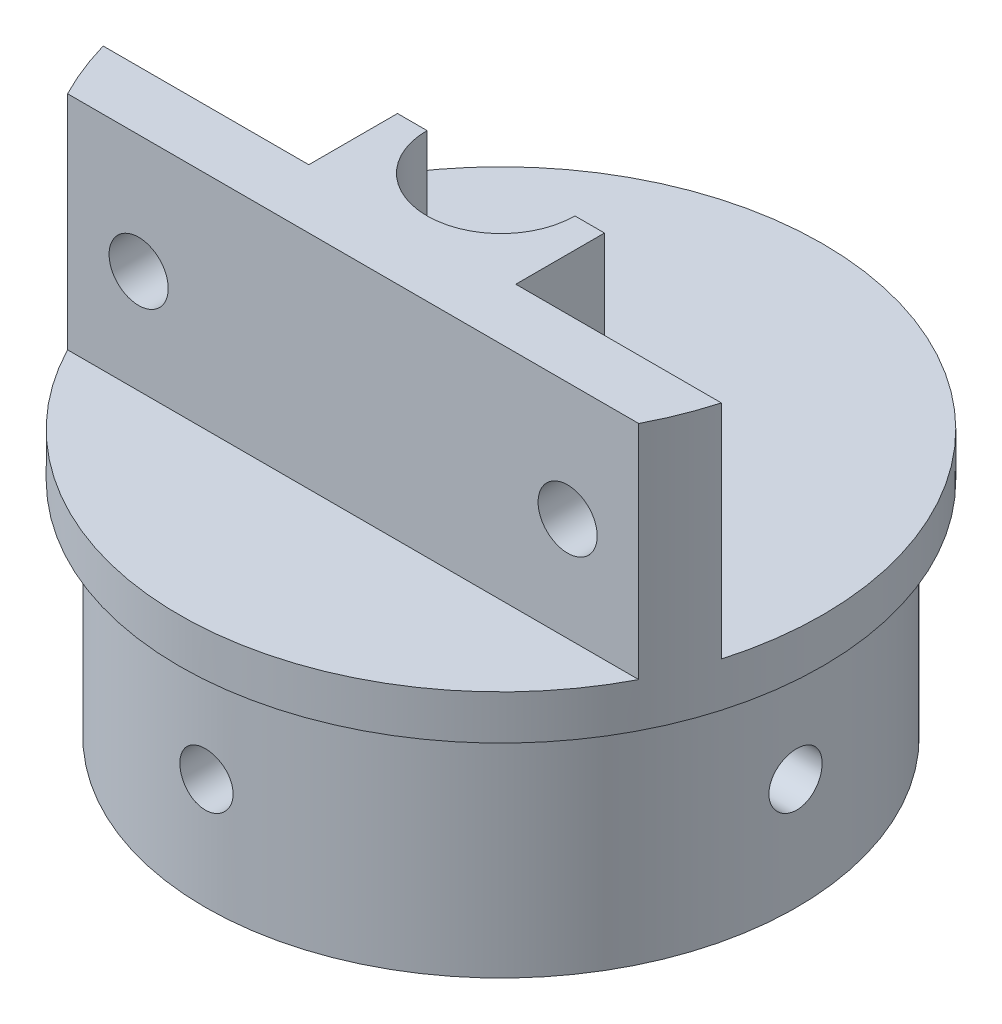
SolidWorks part; units mm, degrees
ref_plane "Front Plane" through (0, 0, 0) normal (0, 0, 1) x (1, 0, 0)
ref_plane "Top Plane" through (0, 0, 0) normal (0, 1, 0) x (1, 0, 0)
ref_plane "Right Plane" through (0, 0, 0) normal (1, 0, 0) x (0, 0, -1)
sketch "Sketch1" plane through (0, 0, 0) normal (0, 1, 0) x (1, 0, 0)
  line L0 (0, 0) -> (25.4, 0) construction
  line L1 (21.9604, 6.35) -> (14.3404, 3.175)
  line L2 (14.3404, 3.175) -> (14.3404, -3.175)
  line L3 (14.3404, -3.175) -> (21.9604, -6.35)
  line L5 (21.9604, 6.35) -> (21.9604, -6.35) construction
  line L6 (6.35, -21.9604) -> (3.175, -14.3404)
  line L7 (3.175, -14.3404) -> (-3.175, -14.3404)
  line L8 (-3.175, -14.3404) -> (-6.35, -21.9604)
  line L9 (-21.9604, -6.35) -> (-14.3404, -3.175)
  line L10 (-14.3404, -3.175) -> (-14.3404, 3.175)
  line L11 (-14.3404, 3.175) -> (-21.9604, 6.35)
  line L12 (-6.35, 21.9604) -> (-3.175, 14.3404)
  line L13 (-3.175, 14.3404) -> (3.175, 14.3404)
  line L14 (3.175, 14.3404) -> (6.35, 21.9604)
  circle A0 centre (0, 0) radius 27.6225 construction
  circle A1 centre (0, 0) radius 25.4
  circle A2 centre (0, 0) radius 22.86
  point P9 (14.3404, 0)
  point P11 (21.9604, 0)
  point P27 (0, 0)
  dimension "D1" = 55.245
  dimension "D2" = 2.2225
  dimension "D3" = 2.54
  dimension "D4" = 6.35
  dimension "D5" = 12.7
  dimension "D6" = 7.62
  dimension "D7" = 4
extrude "tube_connection_ring" add sketch "Sketch1" along normal blind 19.05 contours L14 A2 L12 L13 | L11 A2 L9 L10 | L8 A2 L6 L7 | L3 A2 L1 L2 | A1 A2
ref_plane "Plane1" through (25.4, 0, 0) normal (1, 0, 0) x (0, 0, -1)
sketch "Sketch6" plane through (25.4, 0, 0) normal (1, 0, 0) x (0, 0, -1)
  line L0 (0, 0) -> (0, 9.525) construction
  circle A0 centre (0, 9.525) radius 2.286
  point P4 (0, 9.525)
  dimension "D2" = 4.572
  dimension "D1" = 9.525
extrude "screw_hole" cut sketch "Sketch6" against normal blind 19.05
sketch "Sketch11" plane through (25.4, 0, 0) normal (1, 0, 0) x (0, 0, -1)
  line L0 (0, 9.525) -> (0, 14.9509) construction
  line L1 (0, 4.0991) -> (4.699, 6.812)
  line L2 (4.699, 6.812) -> (4.699, 12.238)
  line L3 (4.699, 12.238) -> (0, 14.9509)
  line L4 (0, 14.9509) -> (-4.699, 12.238)
  line L5 (-4.699, 12.238) -> (-4.699, 6.812)
  line L6 (-4.699, 6.812) -> (0, 4.0991)
  circle A0 centre (0, 9.525) radius 4.699 construction
  dimension "D1" = 9.398
extrude "nut_press_fit_hole" cut sketch "Sketch11" along normal blind 3.81 from surface at -11.0596 starting at face at (14.3404, 9.525, -2.286)
pattern_circular "CirPattern1" count 4 over 360 about axis through (0, 0, 0) along (0, 1, 0) of "screw_hole", "nut_press_fit_hole"
chamfer "screw_hole_chamfer" distance 2.54 angle 45 8 edges at (21.9604, 9.525, 6.35) (6.35, 9.525, 21.9604) (-6.35, 9.525, 21.9604) (21.9604, 9.525, -6.35) (-21.9604, 9.525, 6.35) (-21.9604, 9.525, -6.35) (-6.35, 9.525, -21.9604) (6.35, 9.525, -21.9604)
sketch "Sketch12" plane through (0, 19.05, 0) normal (0, 1, 0) x (1, 0, 0)
  circle A0 centre (0, 0) radius 27.6225
  circle A2 centre (0, 0) radius 3.302
  dimension "D1" = 55.245
  dimension "D2" = 6.604
extrude "top_plate" add sketch "Sketch12" along normal blind 3.81
sketch "Sketch13" plane through (0, 22.86, 0) normal (0, 1, 0) x (1, 0, 0)
  line L1 (26.5507, -7.62) -> (-26.5507, -7.62) construction
  line L2 (14.2621, -28.2316) -> (23.8379, -28.2316) construction
  line L3 (14.2621, -28.2316) -> (14.2621, -39.6616) construction
  line L4 (14.2621, -39.6616) -> (23.8379, -39.6616) construction
  line L5 (23.8379, -28.2316) -> (23.8379, -39.6616) construction
  line L6 (-27.6225, 0) -> (27.6225, 0) construction
  line L7 (27.6225, 6.35) -> (27.6225, -6.35) construction
  line L8 (19.05, 20.0025) -> (19.05, -20.0025) construction
  line L14 (0, -27.6225) -> (0, 0) construction
  line L15 (24.5298, -12.7) -> (-24.5298, -12.7)
  line L22 (26.5507, -7.62) -> (8.89, -7.62)
  line L23 (8.89, -7.62) -> (8.89, 0)
  line L24 (-8.89, 0) -> (-8.89, -7.62)
  line L25 (-8.89, -7.62) -> (-26.5507, -7.62)
  line L26 (-8.89, 0) -> (-6.35, 0)
  line L27 (6.35, 0) -> (8.89, 0)
  circle A0 centre (0, 0) radius 6.35
  circle A1 centre (0, 0) radius 27.6225 construction
  arc A3 (26.5507, -7.62) -> (24.5298, -12.7) centre (0, 0) cw
  arc A4 (-24.5298, -12.7) -> (-26.5507, -7.62) centre (0, 0) ccw
  arc A5 (-24.5298, -12.7) -> (-26.5507, -7.62) centre (0, 0) cw
  point P10 (27.6225, 0)
  point P16 (19.05, -28.2316)
  point P22 (6.35, 0)
  point P27 (-6.35, 0)
  dimension "D4" = 1.27
  dimension "D5" = 12.7
  dimension "D8" = 2.54
  dimension "D1" = 11.43
  dimension "D2" = 9.5758
  dimension "D3" = 12.7
  dimension "D6" = 19.05
  dimension "D7" = 5.08
  dimension "D9" = 2.54
extrude "hinge_hole" add sketch "Sketch13" along normal blind 19.05
sketch "Sketch14" plane through (0, 0, 12.7) normal (0, 0, 1) x (1, 0, 0)
  line L0 (18.4243, 22.86) -> (18.4243, 31.75) construction
  line L1 (27.6225, 22.86) -> (-27.6225, 22.86) construction
  line L2 (0, 22.86) -> (0, 41.91) construction
  line L3 (24.5298, 41.91) -> (-24.5298, 41.91) construction
  line L4 (24.5298, 22.86) -> (-24.5298, 22.86) construction
  circle A0 centre (18.4243, 31.75) radius 2.54
  circle A1 centre (-18.4243, 31.75) radius 2.54
  point P11 (0, 0)
  point P12 (19.1842, 22.86)
  point P15 (18.4243, 22.86)
  dimension "D1" = 5.08
  dimension "D2" = 8.89
extrude "hinge_hole_cut" cut sketch "Sketch14" against normal up to next
